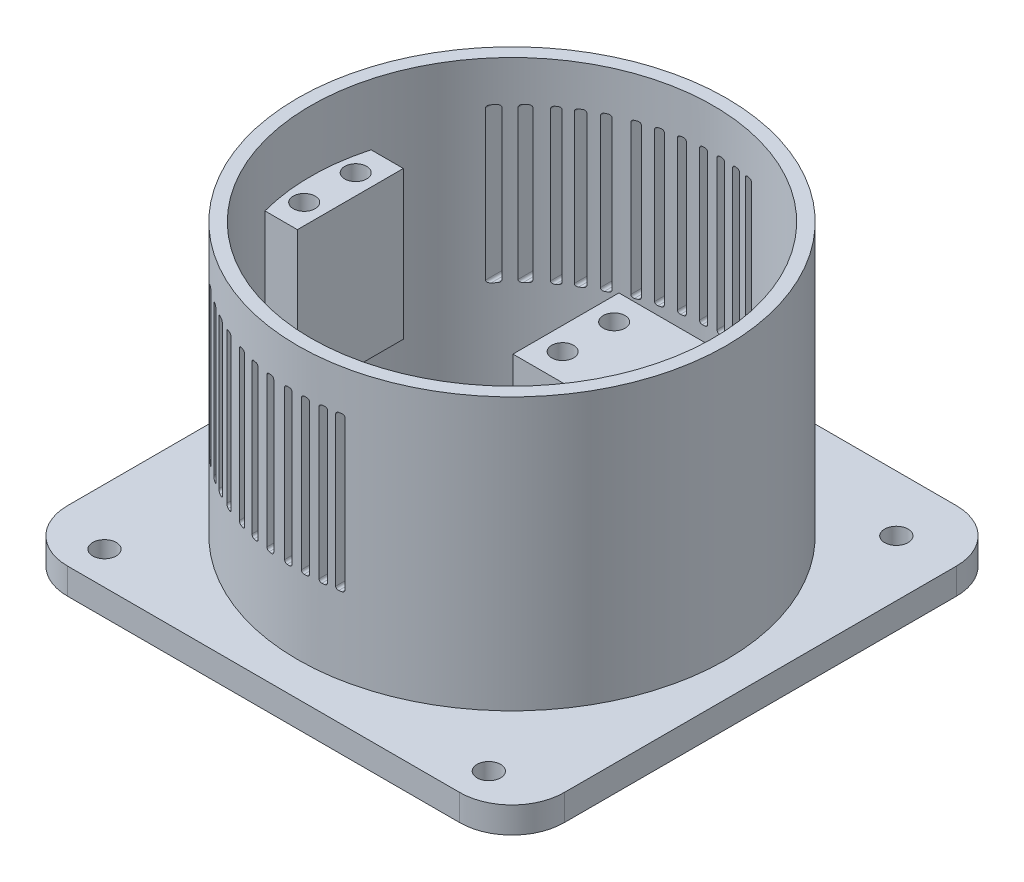
SolidWorks part; units mm, degrees
ref_plane "Front Plane" through (0, 0, 0) normal (0, 0, 1) x (1, 0, 0)
ref_plane "Top Plane" through (0, 0, 0) normal (0, 1, 0) x (1, 0, 0)
ref_plane "Right Plane" through (0, 0, 0) normal (1, 0, 0) x (0, 0, -1)
sketch "Sketch1" plane through (0, 0, 0) normal (0, 1, 0) x (1, 0, 0)
  line L5 (-37.5, 47.5) -> (37.5, 47.5)
  line L6 (-47.5, 37.5) -> (-47.5, -37.5)
  line L7 (-37.5, -47.5) -> (37.5, -47.5)
  line L8 (47.5, 37.5) -> (47.5, -37.5)
  line L9 (-47.5, 47.5) -> (47.5, -47.5) construction
  line L10 (-47.5, -47.5) -> (47.5, 47.5) construction
  circle A2 centre (36.75, 36.75) radius 2.25
  circle A3 centre (-36.75, 36.75) radius 2.25
  circle A4 centre (-36.75, -41.1815) radius 2.25
  circle A5 centre (36.75, -41.1815) radius 2.25
  arc A6 (37.5, 47.5) -> (47.5, 37.5) centre (37.5, 37.5) cw
  arc A7 (37.5, -47.5) -> (47.5, -37.5) centre (37.5, -37.5) ccw
  arc A8 (-37.5, -47.5) -> (-47.5, -37.5) centre (-37.5, -37.5) cw
  arc A9 (-47.5, 37.5) -> (-37.5, 47.5) centre (-37.5, 37.5) cw
  point P0 (0, 0)
  dimension "D1" = 95
  dimension "D4" = 36.75
  dimension "D3" = 10
  dimension "D8" = 4.5
  dimension "D9" = 4.5
  dimension "D10" = 4.5
  dimension "D11" = 4.5
  dimension "D2" = 95
  dimension "D5" = 36.75
  dimension "D6" = 36.75
  dimension "D7" = 36.75
extrude "Boss-Extrude1" add sketch "Sketch1" along normal blind 5 contours A9 L6 A8 L7 A7 L8 A6 L5 A5 A4 A3 A2 region at (0, 0, -0.0159)
sketch "Sketch2" plane through (0, 5, 0) normal (0, 1, 0) x (1, 0, 0)
  circle A0 centre (0, 0) radius 41
extrude "Boss-Extrude2" add sketch "Sketch2" along normal blind 52
sketch "Sketch3" plane through (0, 57, 0) normal (0, 1, 0) x (1, 0, 0)
  circle A0 centre (0, 0) radius 38.5
  dimension "D1" = 77
extrude "Cut-Extrude1" cut sketch "Sketch3" against normal through all
sketch "Sketch4" plane through (0, 17, 0) normal (0, 1, 0) x (1, 0, 0)
  line L0 (10.2692, 10.1739) -> (10.2692, -10.088)
  line L1 (10.2692, -10.088) -> (37.1549, -10.088)
  line L2 (10.2692, 10.1739) -> (37.1314, 10.1739)
  line L3 (-37.1549, -10.088) -> (-30.9538, -10.088)
  line L4 (-30.9538, -10.088) -> (-30.9538, 10.1739)
  line L5 (-30.9538, 10.1739) -> (-37.1314, 10.1739)
  arc A0 (-37.1314, 10.1739) -> (-37.1549, -10.088) centre (0, 0) ccw
  arc A1 (37.1549, -10.088) -> (37.1314, 10.1739) centre (0, 0) ccw
extrude "Boss-Extrude3" add sketch "Sketch4" along normal blind 28.28
sketch "Sketch5" plane through (0, 45.28, 0) normal (0, 1, 0) x (1, 0, 0)
  circle A0 centre (14.6111, 4.925) radius 2.1
  circle A1 centre (14.6111, -4.925) radius 2.1
  circle A2 centre (-34.8111, 4.925) radius 2.1
  circle A3 centre (-34.8111, -4.925) radius 2.1
extrude "Cut-Extrude2" cut sketch "Sketch5" against normal blind 5.5
sketch "Sketch6" plane through (0, 17, 0) normal (0, 1, 0) x (1, 0, 0)
  line L0 (23.7003, 10.1739) -> (10.2692, 10.1739)
  line L1 (37.1314, 10.1739) -> (10.2692, 10.1739) construction
  line L2 (10.2692, 10.1739) -> (10.2692, -10.088)
  line L3 (10.2692, -10.088) -> (23.7003, -10.088)
  line L4 (23.7003, -10.088) -> (23.7003, 10.1739)
extrude "Cut-Extrude3" cut sketch "Sketch6" along normal blind 15
chamfer "Chamfer1" distance 5 angle 45 1 edges at (10.2692, 32, -0.043)
fillet "Fillet2" radius 10 1 edges at (15.2692, 32, -0.043)
sketch "Sketch8" plane through (0, 0, 0) normal (0, 0, 1) x (1, 0, 0)
  line L0 (-20.606, 48.7412) -> (-20.606, 20.2412)
  line L1 (-22.7979, 49.2412) -> (-22.4979, 49.2412)
  line L2 (-23.2979, 48.7412) -> (-23.2979, 20.2412)
  line L3 (-22.7979, 19.7412) -> (-22.4979, 19.7412)
  line L4 (-21.9979, 48.7412) -> (-21.9979, 20.2412)
  line L5 (-20.106, 19.7412) -> (-19.606, 19.7412)
  line L6 (-19.106, 20.2412) -> (-19.106, 48.7412)
  line L7 (-19.606, 49.2412) -> (-20.106, 49.2412)
  line L8 (-17.4266, 48.7412) -> (-17.4266, 20.2412)
  line L9 (-16.9266, 19.7412) -> (-16.4266, 19.7412)
  line L10 (-15.9266, 20.2412) -> (-15.9266, 48.7412)
  line L11 (-16.4266, 49.2412) -> (-16.9266, 49.2412)
  line L12 (-13.3808, 48.7412) -> (-13.3808, 20.2412)
  line L13 (-12.8808, 19.7412) -> (-12.3808, 19.7412)
  line L14 (-11.8808, 20.2412) -> (-11.8808, 48.7412)
  line L15 (-12.3808, 49.2412) -> (-12.8808, 49.2412)
  line L16 (-9.9334, 48.7412) -> (-9.9334, 20.2412)
  line L17 (-9.4334, 19.7412) -> (-8.9334, 19.7412)
  line L18 (-8.4334, 20.2412) -> (-8.4334, 48.7412)
  line L19 (-8.9334, 49.2412) -> (-9.4334, 49.2412)
  line L20 (-6.3427, 48.7412) -> (-6.3427, 20.2412)
  line L21 (-5.8427, 19.7412) -> (-5.3427, 19.7412)
  line L22 (-4.8427, 20.2412) -> (-4.8427, 48.7412)
  line L23 (-5.3427, 49.2412) -> (-5.8427, 49.2412)
  line L24 (-2.56, 48.7412) -> (-2.56, 20.2412)
  line L25 (-2.06, 19.7412) -> (-1.56, 19.7412)
  line L26 (-1.06, 20.2412) -> (-1.06, 48.7412)
  line L27 (-1.56, 49.2412) -> (-2.06, 49.2412)
  line L28 (0.7209, 48.7412) -> (0.7209, 20.2412)
  line L29 (1.2209, 19.7412) -> (1.7209, 19.7412)
  line L30 (2.2209, 20.2412) -> (2.2209, 48.7412)
  line L31 (1.7209, 49.2412) -> (1.2209, 49.2412)
  line L32 (3.8981, 48.7412) -> (3.8981, 20.2412)
  line L33 (4.3981, 19.7412) -> (4.8981, 19.7412)
  line L34 (5.3981, 20.2412) -> (5.3981, 48.7412)
  line L35 (4.8981, 49.2412) -> (4.3981, 49.2412)
  line L36 (6.7244, 48.7412) -> (6.7244, 20.2412)
  line L37 (7.2244, 19.7412) -> (7.7244, 19.7412)
  line L38 (8.2244, 20.2412) -> (8.2244, 48.7412)
  line L39 (7.7244, 49.2412) -> (7.2244, 49.2412)
  line L40 (-25.6496, 49.2412) -> (-26.1496, 49.2412)
  line L41 (-26.6496, 48.7412) -> (-26.6496, 20.2412)
  line L42 (-26.1496, 19.7412) -> (-25.6496, 19.7412)
  line L43 (-25.1496, 20.2412) -> (-25.1496, 48.7412)
  line L44 (-28.6496, 49.2412) -> (-29.1496, 49.2412)
  line L45 (-29.6496, 48.7412) -> (-29.6496, 20.2412)
  line L46 (-29.1496, 19.7412) -> (-28.6496, 19.7412)
  line L47 (-28.1496, 20.2412) -> (-28.1496, 48.7412)
  arc A0 (-22.7979, 19.7412) -> (-23.2979, 20.2412) centre (-22.7979, 20.2412) cw
  arc A1 (-22.4979, 19.7412) -> (-21.9979, 20.2412) centre (-22.4979, 20.2412) ccw
  arc A2 (-21.9979, 48.7412) -> (-22.4979, 49.2412) centre (-22.4979, 48.7412) ccw
  arc A3 (-23.2979, 48.7412) -> (-22.7979, 49.2412) centre (-22.7979, 48.7412) cw
  arc A4 (-28.1496, 20.2412) -> (-28.6496, 19.7412) centre (-28.6496, 20.2412) cw
  arc A5 (-29.1496, 19.7412) -> (-29.6496, 20.2412) centre (-29.1496, 20.2412) cw
  arc A6 (-29.1496, 49.2412) -> (-29.6496, 48.7412) centre (-29.1496, 48.7412) ccw
  arc A7 (-28.1496, 48.7412) -> (-28.6496, 49.2412) centre (-28.6496, 48.7412) ccw
  arc A8 (-26.1496, 19.7412) -> (-26.6496, 20.2412) centre (-26.1496, 20.2412) cw
  arc A9 (-25.1496, 20.2412) -> (-25.6496, 19.7412) centre (-25.6496, 20.2412) cw
  arc A10 (-26.1496, 49.2412) -> (-26.6496, 48.7412) centre (-26.1496, 48.7412) ccw
  arc A11 (-25.6496, 49.2412) -> (-25.1496, 48.7412) centre (-25.6496, 48.7412) cw
  arc A12 (-19.606, 19.7412) -> (-19.106, 20.2412) centre (-19.606, 20.2412) ccw
  arc A13 (-20.106, 19.7412) -> (-20.606, 20.2412) centre (-20.106, 20.2412) cw
  arc A14 (-19.106, 48.7412) -> (-19.606, 49.2412) centre (-19.606, 48.7412) ccw
  arc A15 (-20.606, 48.7412) -> (-20.106, 49.2412) centre (-20.106, 48.7412) cw
  arc A16 (-16.4266, 19.7412) -> (-15.9266, 20.2412) centre (-16.4266, 20.2412) ccw
  arc A17 (-16.9266, 19.7412) -> (-17.4266, 20.2412) centre (-16.9266, 20.2412) cw
  arc A18 (-16.9266, 49.2412) -> (-17.4266, 48.7412) centre (-16.9266, 48.7412) ccw
  arc A19 (-15.9266, 48.7412) -> (-16.4266, 49.2412) centre (-16.4266, 48.7412) ccw
  arc A20 (-12.3808, 19.7412) -> (-11.8808, 20.2412) centre (-12.3808, 20.2412) ccw
  arc A21 (-12.8808, 19.7412) -> (-13.3808, 20.2412) centre (-12.8808, 20.2412) cw
  arc A22 (-12.8808, 49.2412) -> (-13.3808, 48.7412) centre (-12.8808, 48.7412) ccw
  arc A23 (-11.8808, 48.7412) -> (-12.3808, 49.2412) centre (-12.3808, 48.7412) ccw
  arc A24 (-9.9334, 20.2412) -> (-9.4334, 19.7412) centre (-9.4334, 20.2412) ccw
  arc A25 (-9.4334, 49.2412) -> (-9.9334, 48.7412) centre (-9.4334, 48.7412) ccw
  arc A26 (-8.9334, 19.7412) -> (-8.4334, 20.2412) centre (-8.9334, 20.2412) ccw
  arc A27 (-5.3427, 19.7412) -> (-4.8427, 20.2412) centre (-5.3427, 20.2412) ccw
  arc A28 (-6.3427, 20.2412) -> (-5.8427, 19.7412) centre (-5.8427, 20.2412) ccw
  arc A29 (-4.8427, 48.7412) -> (-5.3427, 49.2412) centre (-5.3427, 48.7412) ccw
  arc A30 (-6.3427, 48.7412) -> (-5.8427, 49.2412) centre (-5.8427, 48.7412) cw
  arc A31 (-2.06, 19.7412) -> (-2.56, 20.2412) centre (-2.06, 20.2412) cw
  arc A32 (-1.06, 20.2412) -> (-1.56, 19.7412) centre (-1.56, 20.2412) cw
  arc A33 (-2.06, 49.2412) -> (-2.56, 48.7412) centre (-2.06, 48.7412) ccw
  arc A34 (-1.06, 48.7412) -> (-1.56, 49.2412) centre (-1.56, 48.7412) ccw
  arc A35 (1.2209, 19.7412) -> (0.7209, 20.2412) centre (1.2209, 20.2412) cw
  arc A36 (2.2209, 20.2412) -> (1.7209, 19.7412) centre (1.7209, 20.2412) cw
  arc A37 (1.2209, 49.2412) -> (0.7209, 48.7412) centre (1.2209, 48.7412) ccw
  arc A38 (2.2209, 48.7412) -> (1.7209, 49.2412) centre (1.7209, 48.7412) ccw
  arc A39 (4.3981, 19.7412) -> (3.8981, 20.2412) centre (4.3981, 20.2412) cw
  arc A40 (5.3981, 20.2412) -> (4.8981, 19.7412) centre (4.8981, 20.2412) cw
  arc A41 (4.3981, 49.2412) -> (3.8981, 48.7412) centre (4.3981, 48.7412) ccw
  arc A42 (5.3981, 48.7412) -> (4.8981, 49.2412) centre (4.8981, 48.7412) ccw
  arc A43 (7.2244, 19.7412) -> (6.7244, 20.2412) centre (7.2244, 20.2412) cw
  arc A44 (8.2244, 20.2412) -> (7.7244, 19.7412) centre (7.7244, 20.2412) cw
  arc A45 (7.2244, 49.2412) -> (6.7244, 48.7412) centre (7.2244, 48.7412) ccw
  arc A46 (8.2244, 48.7412) -> (7.7244, 49.2412) centre (7.7244, 48.7412) ccw
  arc A47 (-8.4334, 48.7412) -> (-8.9334, 49.2412) centre (-8.9334, 48.7412) ccw
  point P6 (-23.2979, 19.7412)
  point P9 (-21.9979, 19.7412)
  point P12 (-21.9979, 49.2412)
  point P73 (-26.6496, 49.2412)
  dimension "D3" = 0.5
  dimension "D7" = 0.5
  dimension "D8" = 0.5
  dimension "D9" = 0.5
  dimension "D10" = 0.5
  dimension "D11" = 0.5
  dimension "D12" = 0.5
  dimension "D13" = 0.5
  dimension "D14" = 0.5
  dimension "D15" = 0.5
  dimension "D16" = 0.5
  dimension "D17" = 0.5
  dimension "D18" = 0.5
  dimension "D1" = 29.5
  dimension "D2" = 1.3
  dimension "D4" = 1.5
  dimension "D5" = 1.5
  dimension "D6" = 1.5
  dimension "D19" = 1.5
  dimension "D20" = 1.8517
extrude "Cut-Extrude5" cut sketch "Sketch8" against normal through all both and the other way through all
